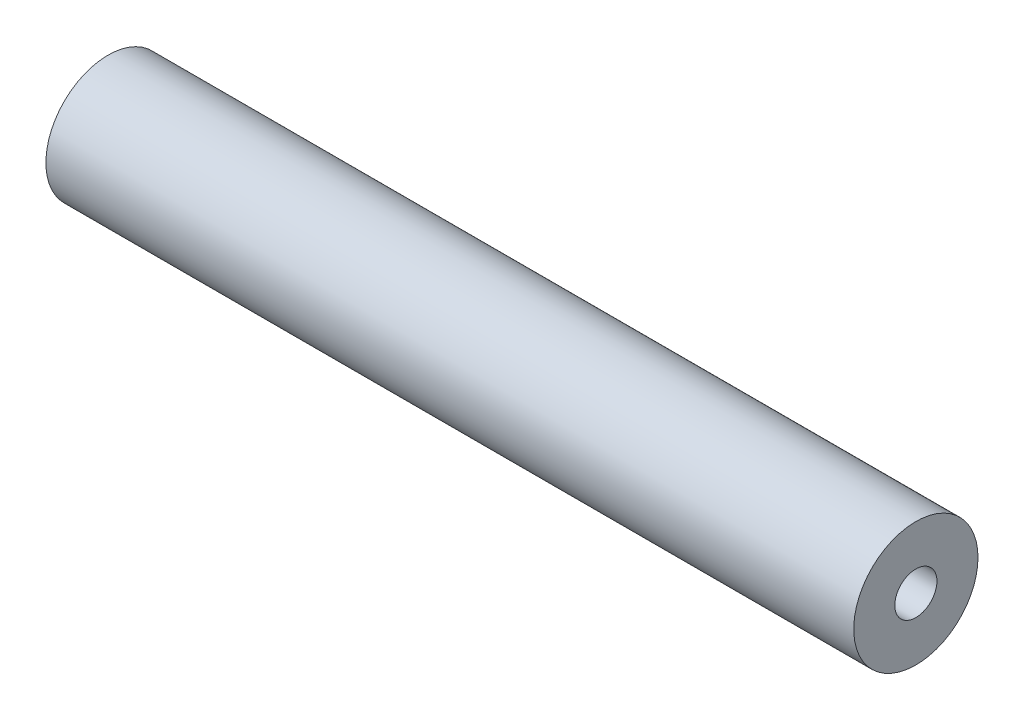
SolidWorks part; units mm, degrees
ref_plane "Front Plane" through (0, 0, 0) normal (0, 0, 1) x (1, 0, 0)
ref_plane "Top Plane" through (0, 0, 0) normal (0, 1, 0) x (1, 0, 0)
ref_plane "Right Plane" through (0, 0, 0) normal (1, 0, 0) x (0, 0, -1)
sketch "Sketch1" plane through (0, 0, 0) normal (1, 0, 0) x (0, 0, -1)
  circle A0 centre (0, 0) radius 6.35
  circle A1 centre (0, 0) radius 2.1526
  dimension "D1" = 12.7
  dimension "D2" = 4.3053
extrude "Boss-Extrude1" add sketch "Sketch1" along normal blind 82.55
